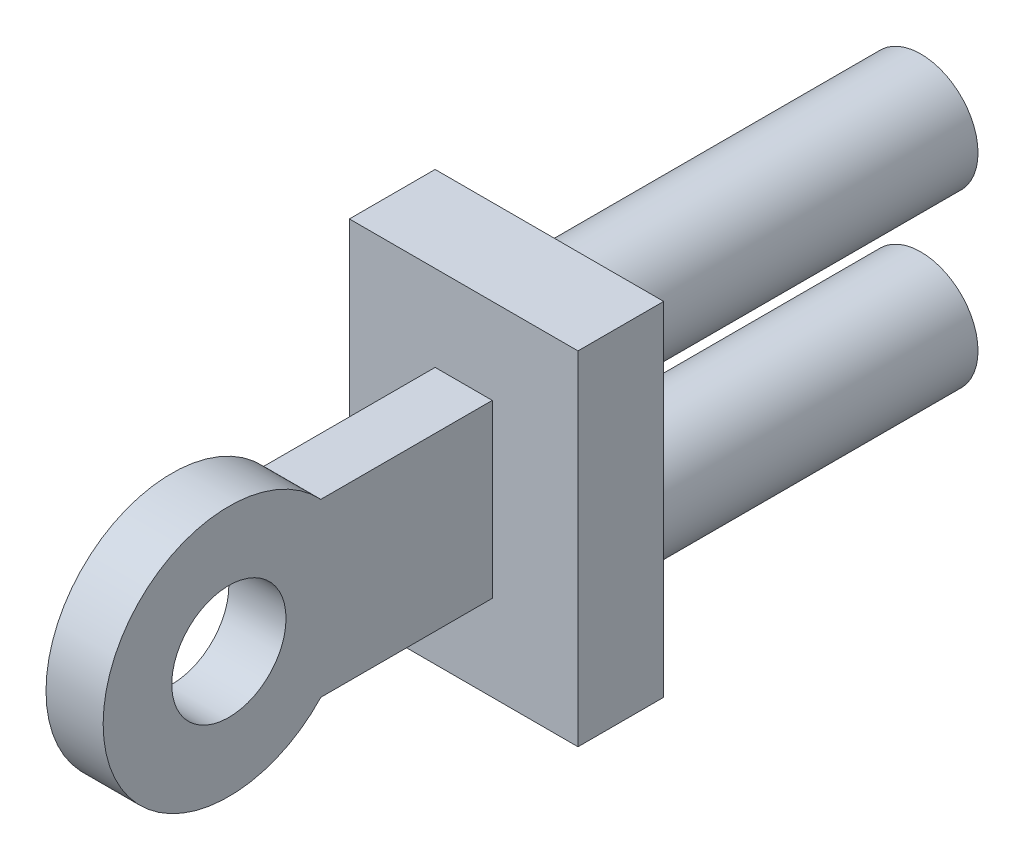
SolidWorks part; units mm, degrees
ref_plane "Front Plane" through (0, 0, 0) normal (0, 0, 1) x (1, 0, 0)
ref_plane "Top Plane" through (0, 0, 0) normal (0, 1, 0) x (1, 0, 0)
ref_plane "Right Plane" through (0, 0, 0) normal (1, 0, 0) x (0, 0, -1)
sketch "Sketch1" plane through (0, 0, 0) normal (0, 0, 1) x (1, 0, 0)
  line L1 (2, 3) -> (-2, 3)
  line L2 (2, 3) -> (2, -3)
  line L3 (2, -3) -> (-2, -3)
  line L4 (-2, 3) -> (-2, -3)
  line L5 (2, 3) -> (-2, -3) construction
  line L6 (2, -3) -> (-2, 3) construction
  line L11 (1.6, 2) -> (1.1, -2) construction
  dimension "D1" = 4
  dimension "D2" = 6
extrude "Boss-Extrude1" add sketch "Sketch1" along normal blind 1.5
sketch "Sketch2" plane through (2, 0, 0) normal (1, 0, 0) x (0, 0, -1)
  line L0 (-1.5, 1.5) -> (-4.5, 1.5)
  line L1 (-1.5, -3) -> (-1.5, 3) construction
  line L3 (-4.5, -1.5) -> (-1.5, -1.5)
  line L4 (-1.5, -1.5) -> (-1.5, 1.5)
  line L5 (-6.1093, 0) -> (0, 0) construction
  arc A0 (-4.5, 1.5) -> (-4.5, -1.5) centre (-6.1093, 0) ccw
  circle A1 centre (-6.1093, 0) radius 1
  dimension "D2" = 2
  dimension "D3" = 2.2
  dimension "D1" = 3
  dimension "D4" = 3
extrude "Boss-Extrude2" add sketch "Sketch2" against normal blind 0.5 and the other way blind 0.5 from surface starting at plane "Right Plane"
sketch "Sketch3" plane through (0, 0, 0) normal (0, 0, -1) x (-1, 0, 0)
  line L0 (0, 1.5) -> (0, -1.5) construction
  circle A0 centre (0, 1.5) radius 1
  circle A1 centre (0, -1.5) radius 1
  point P5 (0, 0)
  dimension "D1" = 2
  dimension "D2" = 2
  dimension "D3" = 3
extrude "Boss-Extrude3" add sketch "Sketch3" along normal blind 6.5
